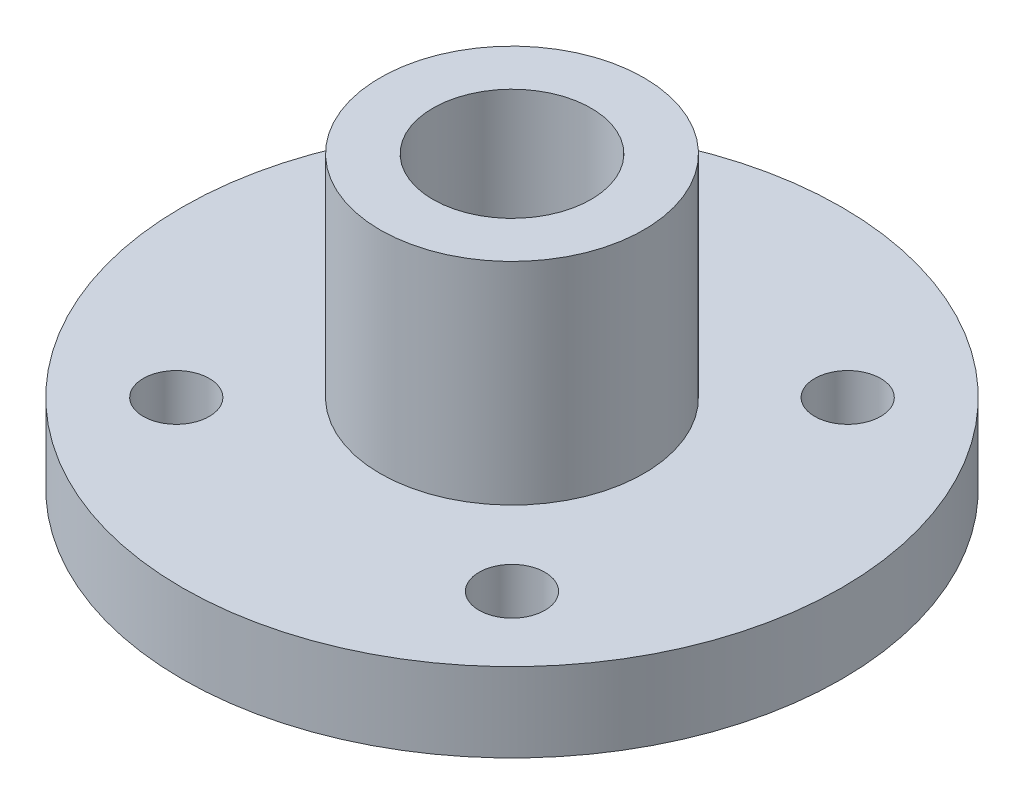
SolidWorks part; units mm, degrees
note: The reader was unsure of these and kept them because the rebuilt part matched: shared geometry of "Croquis1<3>".
ref_plane "Alzado" through (0, 0, 0) normal (0, 0, 1) x (1, 0, 0)
ref_plane "Planta" through (0, 0, 0) normal (0, 1, 0) x (1, 0, 0)
ref_plane "Vista lateral" through (0, 0, 0) normal (1, 0, 0) x (0, 0, -1)
sketch "Croquis1" plane through (0, 0, 0) normal (0, 1, 0) x (1, 0, 0)
  line L0 (0, 0) -> (-6.6149, 6.6149) construction
  line L1 (-6.6149, 6.6149) -> (7.3418, -7.3418) construction
  line L2 (0, 0) -> (-6.786, -6.786) construction
  line L3 (-6.786, -6.786) -> (7.1299, 7.1299) construction
  circle A0 centre (0, 0) radius 12.5
  circle A1 centre (-6.364, 6.364) radius 1.25
  circle A3 centre (2.3431, -13.6569) radius 1.25
  circle A5 centre (0, 0) radius 3
  circle A6 centre (0, 0) radius 5
  circle A7 centre (6.364, 6.364) radius 1.25
  circle A8 centre (6.364, -6.364) radius 1.25
  circle A9 centre (-6.364, -6.364) radius 1.25
  point P14 (-1.6569, -4)
  point P23 (0, 0)
  dimension "D1" = 25
  dimension "D2" = 2.5
  dimension "D4" = 9
  dimension "D5" = 6
  dimension "D6" = 10
  dimension "D7" = 45
  dimension "D3" = 4
extrude "Saliente-Extruir1" add sketch "Croquis1" along normal blind 3
extrude "Saliente-Extruir2" add sketch "Croquis1<3>" along normal blind 8 from surface at 3 contours A6 | A5 starting at face at (-6.364, 3, 7.614)
sketch "Croquis1<3>" plane through (0, 0, 0) normal (0, 1, 0) x (1, 0, 0) same geometry as "Croquis1"
sketch "Croquis2" plane through (0, 0, 0) normal (1, 0, 0) x (0, 0, -1)
  line L0 (3, 11) -> (-3, 11) construction
  circle A0 centre (0, 6) radius 1.5
  point P4 (0, 6)
  dimension "D1" = 3
  dimension "D2" = 5
extrude "Cortar-Extruir1" cut sketch "Croquis2" against normal through all
ref_plane "Plano3" through (-5, 0, 0) normal (-1, 0, 0) x (0, 0, 1)
thread "Rosca2" [suppressed] pitch 0.5 start angle 0, offset 0, length 1.5, pitch 0.5, diameter 2
ref_plane "Plano4" through (-5, 6, -1) normal (0, -1, 0) x (0, 0, -1)
sketch "Perfil de rosca3" plane through (-5, 6, -1) normal (0, -1, 0) x (0, 0, -1)
  line L0 (0, 0) -> (0, 0.5) construction
  line L11 (0, 0) -> (0, 0.4375)
  line L12 (0, 0.4375) -> (-0.2706, 0.2812)
  line L13 (-0.2706, 0.2812) -> (-0.2706, 0.1562)
  line L15 (-0.2706, 0.1562) -> (0, 0)
  line L17 (-0.2706, 0.2187) -> (0, 0.2187) construction
  point P2 (0, 0)
  dimension "Pitch" = 0.5
  dimension "Profile_Angle" = 60
  dimension "Profile_Land" = 0.125
  dimension "Profile_Height" = 0.2706
